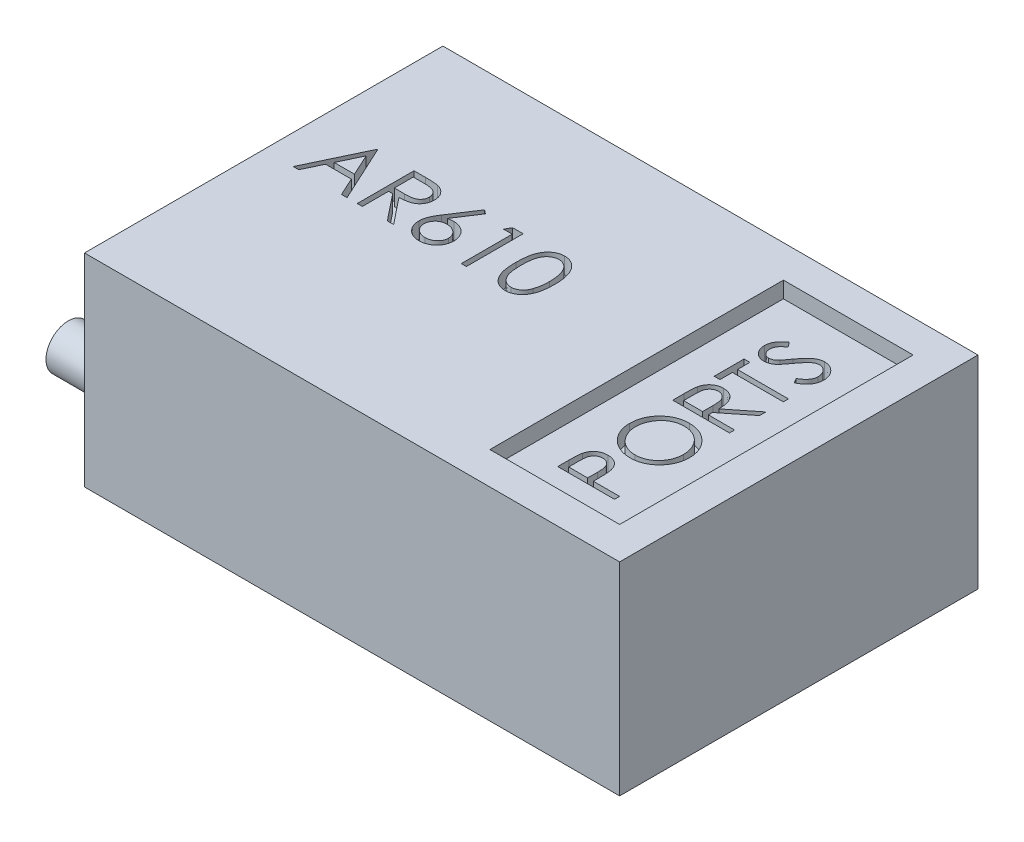
SolidWorks part; units mm, degrees
ref_plane "Front Plane" through (0, 0, 0) normal (0, 0, 1) x (1, 0, 0)
ref_plane "Top Plane" through (0, 0, 0) normal (0, 1, 0) x (1, 0, 0)
ref_plane "Right Plane" through (0, 0, 0) normal (1, 0, 0) x (0, 0, -1)
ref_axis "X" through (-88.99, 0, 0) along (1, 0, 0)
ref_axis "Y" through (0, 55, 0) along (0, -1, 0)
ref_axis "Z" through (0, 0, -88.99) along (0, 0, 1)
sketch "Sketch1" plane through (0, 0, 0) normal (0, 1, 0) x (1, 0, 0)
  line L0 (0, 0) -> (10.5, 0) construction
  line L1 (-16.5, 11.05) -> (16.5, 11.05)
  line L2 (-16.5, 11.05) -> (-16.5, -11.05)
  line L3 (-16.5, -11.05) -> (16.5, -11.05)
  line L4 (16.5, 11.05) -> (16.5, -11.05)
  line L5 (-16.5, 11.05) -> (16.5, -11.05) construction
  line L6 (-16.5, -11.05) -> (16.5, 11.05) construction
  line L7 (14.5, 9.05) -> (14.5, 11.05) construction
  line L8 (6.5, 9.05) -> (14.5, 9.05)
  line L9 (6.5, 9.05) -> (6.5, -9.05)
  line L10 (6.5, -9.05) -> (14.5, -9.05)
  line L11 (14.5, 9.05) -> (14.5, -9.05)
  line L12 (6.5, 9.05) -> (14.5, -9.05) construction
  line L13 (6.5, -9.05) -> (14.5, 9.05) construction
  line L14 (14.5, 9.05) -> (16.5, 9.05) construction
  point P0 (0, 0)
  dimension "D1" = 22.1
  dimension "D2" = 33
  dimension "D3" = 8
  dimension "D4" = 2
extrude "Boss-Extrude1" add sketch "Sketch1" along normal blind 12.5 contours L2 L3 L4 L1
extrude "Cut-Extrude1" cut sketch "Sketch1<3>" against normal blind 1 from surface contours L11 L8 L9 L10 region at (10.5, 0, 0) starting at face at (0, 12.5, 0)
sketch "Sketch1<3>" plane through (0, 0, 0) normal (0, 1, 0) x (1, 0, 0) same geometry as "Sketch1"
sketch "Sketch2" plane through (0, 11.5, 0) normal (0, 1, 0) x (1, 0, 0)
  line L0 (0, 0) -> (12, 0) construction
  line L1 (12, 8) -> (12, -8) construction
  text T0 "PORTS"
  point P6 (12, 0)
  dimension "D1" = 12
  dimension "D2" = 16
extrude "Cut-Extrude2" cut sketch "Sketch2" against normal blind 1
sketch "Sketch3" plane through (0, 12.5, 0) normal (0, 1, 0) x (1, 0, 0)
  line L0 (0, 0) -> (-15, 0) construction
  text T0 "AR610"
  dimension "D1" = 15
extrude "Cut-Extrude3" cut sketch "Sketch3" against normal blind 1
sketch "Sketch4" plane through (-16.5, 0, 0) normal (-1, 0, 0) x (0, 0, 1)
  line L0 (8.05, 0) -> (8.05, 4) construction
  line L1 (-11.05, 0) -> (11.05, 0) construction
  line L2 (8.05, 4) -> (11.05, 4) construction
  line L3 (11.05, 12.5) -> (11.05, 0) construction
  circle A0 centre (8.05, 4) radius 1.375
  dimension "D3" = 2.75
  dimension "D1" = 4
  dimension "D2" = 3
extrude "Boss-Extrude2" add sketch "Sketch4" along normal blind 4
sketch "Sketch5" plane through (0, 0, -11.05) normal (0, 0, -1) x (-1, 0, 0)
  line L0 (13.5, 0) -> (13.5, 4) construction
  line L1 (16.5, 0) -> (-16.5, 0) construction
  line L2 (13.5, 4) -> (16.5, 4) construction
  line L4 (16.5, 12.5) -> (16.5, 0) construction
  circle A0 centre (13.5, 4) radius 1.375
  dimension "D3" = 2.75
  dimension "D1" = 4
  dimension "D2" = 3
extrude "Boss-Extrude3" add sketch "Sketch5" along normal blind 4
